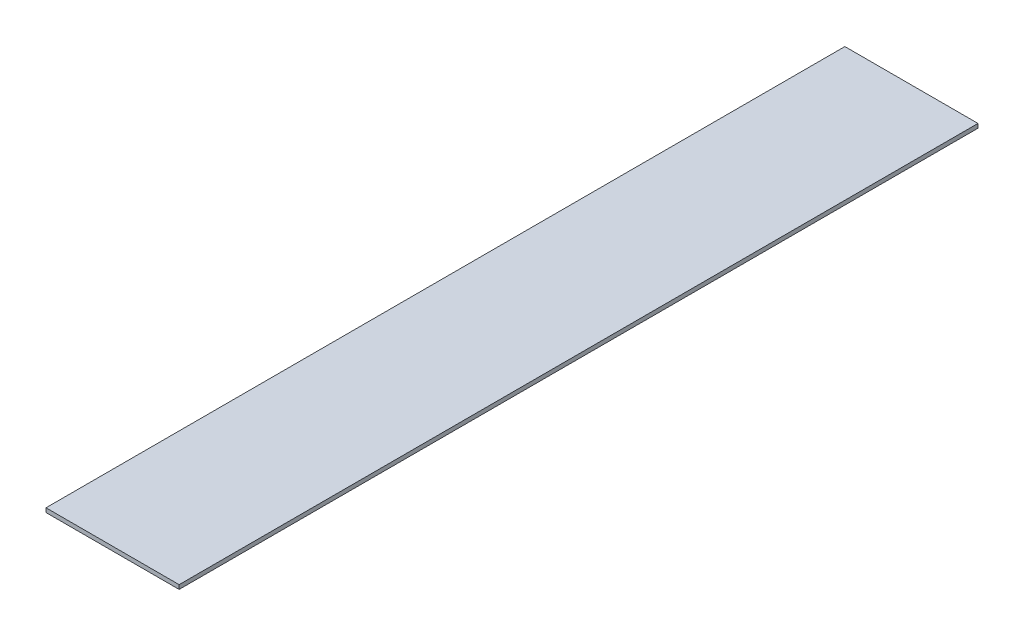
SolidWorks part; units mm, degrees
material "NEOPRENE"
ref_plane "Front Plane" through (0, 0, 0) normal (0, 0, 1) x (1, 0, 0)
ref_plane "Top Plane" through (0, 0, 0) normal (0, 1, 0) x (1, 0, 0)
ref_plane "Right Plane" through (0, 0, 0) normal (1, 0, 0) x (0, 0, -1)
sketch "Sketch1" plane through (0, 0, 0) normal (0, 0, 1) x (1, 0, 0)
  line L0 (0, 0.3969) -> (0, -0.3969)
  line L1 (-12.7, 0) -> (12.7, 0) construction
  point P6 (0, 0)
  dimension "Width" = 25.4
  dimension "Thk" = 0.7937
sketch "Sketch2" plane through (0, 0, 0) normal (1, 0, 0) x (0, 0, -1)
  line L0 (76.2, 0) -> (-76.2, 0)
  point P4 (0, 0)
  dimension "Length" = 152.4
sketch "Sketch3" plane through (0, 0, 0) normal (0, 0, 1) x (1, 0, 0)
  line L1 (12.7, 0.3969) -> (-12.7, 0.3969)
  line L2 (12.7, 0.3969) -> (12.7, -0.3969)
  line L3 (12.7, -0.3969) -> (-12.7, -0.3969)
  line L4 (-12.7, 0.3969) -> (-12.7, -0.3969)
  line L5 (12.7, 0.3969) -> (-12.7, -0.3969) construction
  line L6 (12.7, -0.3969) -> (-12.7, 0.3969) construction
  point P0 (0, 0)
extrude "Boss-Extrude1" add sketch "Sketch3" along normal up to vertex (76.2 mm away) and the other way up to vertex (76.2 mm away) up to point (0, 0, 76.2) other way up to point (0, 0, -76.2)
sketch "Sketch4" plane through (0, 0.3969, 0) normal (0, 1, 0) x (1, 0, 0)
  line L5 (7.5828, -11.6745) -> (-7.5828, -11.6745)
  line L6 (7.5828, -11.6745) -> (7.5828, 11.6745)
  line L7 (7.5828, 11.6745) -> (-7.5828, 11.6745)
  line L8 (-7.5828, -11.6745) -> (-7.5828, 11.6745)
  line L9 (7.5828, -11.6745) -> (-7.5828, 11.6745) construction
  line L10 (7.5828, 11.6745) -> (-7.5828, -11.6745) construction
  line L11 (12.7, -76.2) -> (-12.7, -76.2)
  line L12 (12.7, -76.2) -> (12.7, 76.2)
  line L13 (12.7, 76.2) -> (-12.7, 76.2)
  line L14 (-12.7, -76.2) -> (-12.7, 76.2)
  line L15 (12.7, -76.2) -> (-12.7, 76.2) construction
  line L16 (12.7, 76.2) -> (-12.7, -76.2) construction
  point P0 (0, 0)
  point P5 (0, 0)
  dimension "D3" = 23.3489
  dimension "D4" = 15.1657
extrude "Cut-Extrude1" [suppressed] cut sketch "Sketch4" against normal through all
